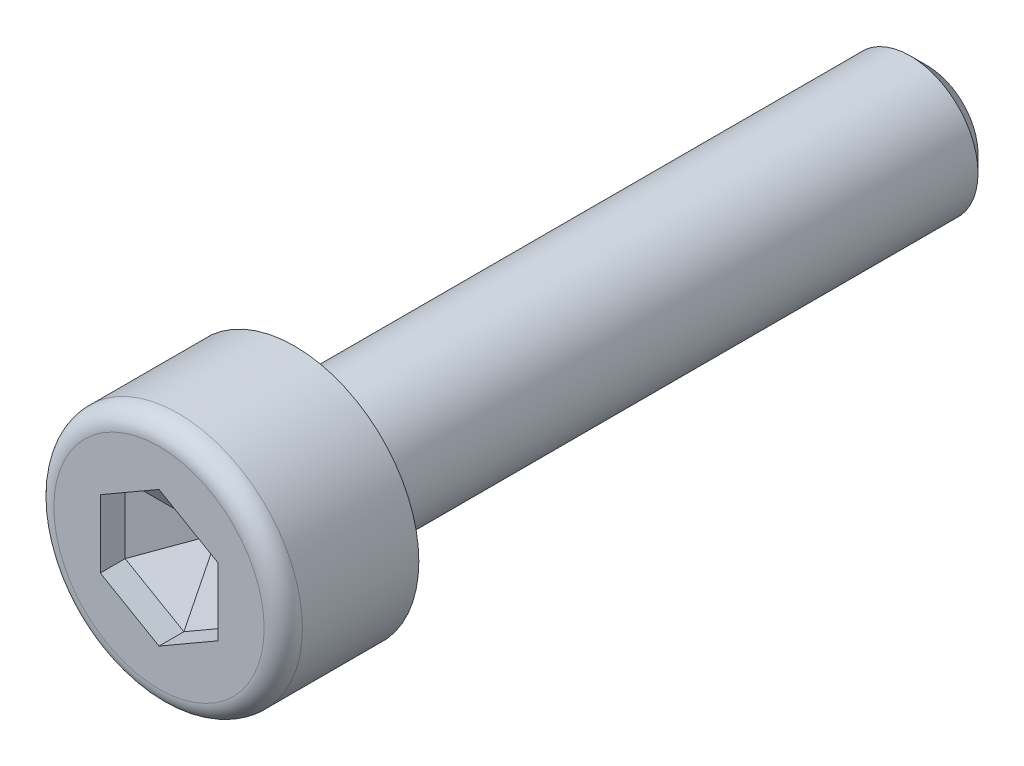
SolidWorks part; units mm, degrees
ref_plane "前视基准面" through (0, 0, 0) normal (0, 0, 1) x (1, 0, 0)
ref_plane "上视基准面" through (0, 0, 0) normal (0, 1, 0) x (1, 0, 0)
ref_plane "右视基准面" through (0, 0, 0) normal (1, 0, 0) x (0, 0, -1)
sketch "草图1" plane through (0, 0, 0) normal (0, 0, 1) x (1, 0, 0)
  circle A0 centre (0, 0) radius 2.75
  dimension "dk" = 5.5
extrude "凸台-拉伸1" add sketch "草图1" along normal blind 3
ref_axis "基准轴1" through (0, 0, 3) along (0, 0, -1)
sketch "草图2" plane through (0, 0, 3) normal (0, 0, 1) x (1, 0, 0)
  line L1 (1.3, 0.7506) -> (0, 1.5011)
  line L2 (0, 1.5011) -> (-1.3, 0.7506)
  line L3 (-1.3, 0.7506) -> (-1.3, -0.7506)
  line L4 (-1.3, -0.7506) -> (0, -1.5011)
  line L5 (0, -1.5011) -> (1.3, -0.7506)
  line L6 (1.3, -0.7506) -> (1.3, 0.7506)
  circle A0 centre (0, 0) radius 1.3 construction
  dimension "s" = 2.6
extrude "切除-拉伸1" cut sketch "草图2" against normal blind 1.3
sketch "草图3" plane through (0, 0, 0) normal (0, 0, -1) x (-1, 0, 0)
  circle A0 centre (0, 0) radius 1.5
  dimension "d" = 3
extrude "凸台-拉伸2" add sketch "草图3" along normal blind 14
cosmetic thread "装饰螺纹线1" parameters "b"=4.9, "D2"=1.221
chamfer "倒角1" distance 0.375 angle 45 1 edges at (-1.5, 0, -14)
fillet "圆角1" radius 0.4231 1 edges at (2.75, 0, 3)
chamfer "倒角2" distance 0.7493 angle 60 6 edges at (-1.3, 0, 1.7) (-0.65, 1.1258, 1.7) (0.65, 1.1258, 1.7) (1.3, 0, 1.7) (-0.65, -1.1258, 1.7) (0.65, -1.1258, 1.7) first distance on face at (-1.3, 0, 2.35) first distance on face at (-0.65, 1.1258, 2.35) first distance on face at (0.65, 1.1258, 2.35) first distance on face at (1.3, 0, 2.35) first distance on face at (-0.65, -1.1258, 2.35) first distance on face at (0.65, -1.1258, 2.35)
fillet "圆角2" radius 0.1 1 edges at (1.5, 0, 0)
ref_plane "基准面1" through (0, 0, 0) normal (0, 0, -1) x (-1, 0, 0)
equation "\"D1@倒角2\" = \"s@草图2\" / 3.47"
equation "\"D1@圆角1\"= \"dk@草图1\" / 13"
equation "\"D1@倒角1\"= \"d@草图3\" / 8"
equation "\"D1@圆角2\"= \"d@草图3\" / \"d@草图3\" * 0.1"
